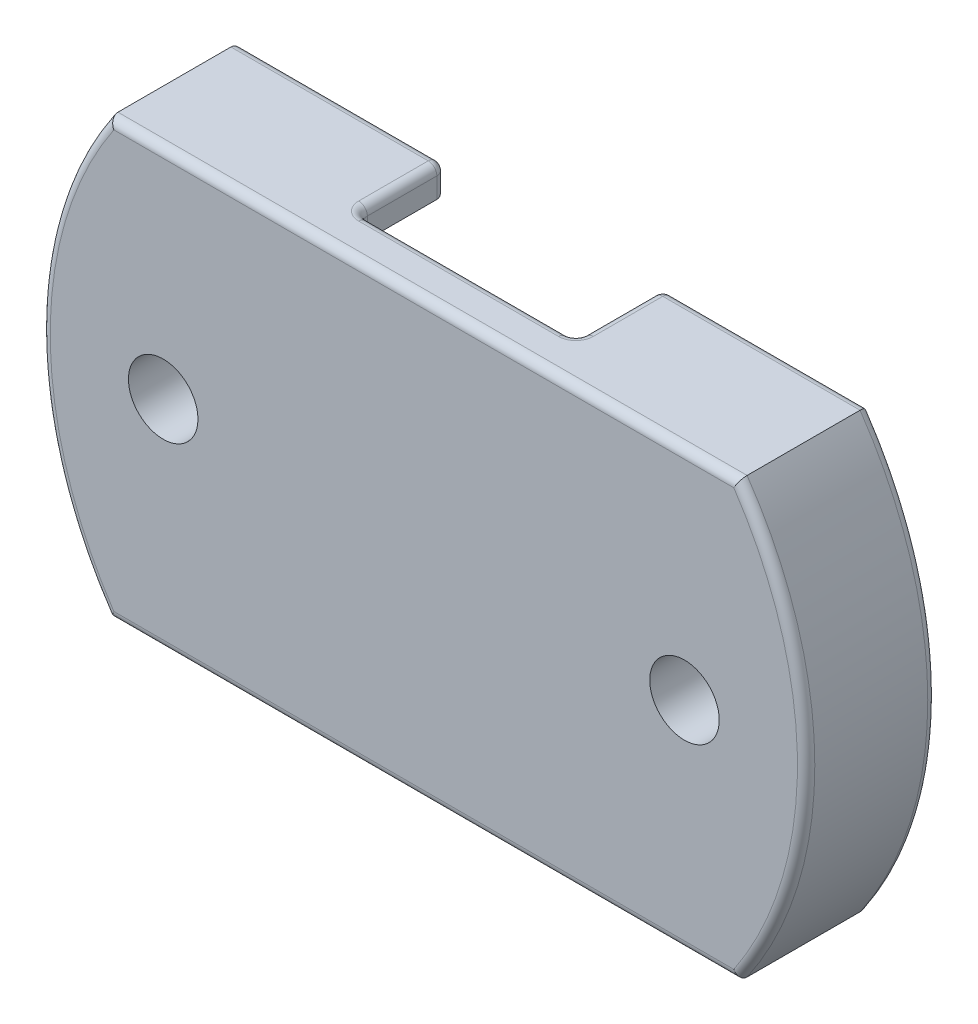
SolidWorks part; units mm, degrees
ref_plane "Front Plane" through (0, 0, 0) normal (0, 0, 1) x (1, 0, 0)
ref_plane "Top Plane" through (0, 0, 0) normal (0, 1, 0) x (1, 0, 0)
ref_plane "Right Plane" through (0, 0, 0) normal (1, 0, 0) x (0, 0, -1)
sketch "Sketch1" plane through (0, 0, 0) normal (0, 0, 1) x (1, 0, 0)
  line L0 (-73.039, 0) -> (73.039, 0) construction
  line L1 (-73.039, -25) -> (73.039, -25)
  line L2 (-73.039, 25) -> (73.039, 25)
  circle A0 centre (0, 0) radius 30
  circle A1 centre (-30, 0) radius 4
  circle A2 centre (30, 0) radius 4
  circle A3 centre (0, 0) radius 44
  circle A4 centre (0, 0) radius 17.5
  dimension "D1" = 60
  dimension "D2" = 8
  dimension "D3" = 88
  dimension "D6" = 35
  dimension "D4" = 25
  dimension "D5" = 25
sketch "Sketch2" plane through (0, 0, 0) normal (0, 0, 1) x (1, 0, 0)
  line L0 (-73.039, 25) -> (73.039, 25) construction
  line L1 (-73.039, -25) -> (73.039, -25) construction
  line L2 (-36.2077, 25) -> (36.2077, 25)
  line L3 (-36.2077, -25) -> (36.2077, -25)
  arc A0 (36.2077, -25) -> (36.2077, 25) centre (0, 0) ccw
  circle A1 centre (0, 0) radius 44
  arc A2 (-36.2077, 25) -> (-36.2077, -25) centre (0, 0) ccw
  dimension "D1" = 0
extrude "Boss-Extrude1" add sketch "Sketch2" along normal blind 15
sketch "Sketch3" plane through (0, 0, 0) normal (0, 0, 1) x (1, 0, 0)
  line L0 (12.5, 21.6506) -> (12.5, 42.5593)
  line L5 (12.5, -42.5593) -> (-12.5, -42.5593)
  line L6 (12.5, -42.5593) -> (12.5, -21.6506)
  line L7 (12.5, 42.5593) -> (-12.5, 42.5593)
  line L8 (-12.5, -42.5593) -> (-12.5, -21.6506)
  line L9 (12.5, -42.5593) -> (-12.5, 42.5593) construction
  line L10 (12.5, 42.5593) -> (-12.5, -42.5593) construction
  line L11 (-12.5, 21.6506) -> (-12.5, 42.5593)
  arc A0 (-12.5, 21.6506) -> (-12.5, -21.6506) centre (0, 0) ccw
  arc A3 (12.5, -21.6506) -> (12.5, 21.6506) centre (0, 0) ccw
  dimension "D1" = 50
  dimension "D2" = 25
extrude "Cut-Extrude1" cut sketch "Sketch3" along normal blind 10
fillet "Fillet1" radius 1 24 edges at (0, -25, 10) (0, 25, 10) (-24.3539, 25, 0) (-44, 0, 0) (-24.3539, -25, 0) (24.3539, -25, 0) (44, 0, 0) (24.3539, 25, 0) (12.5, 25, 5) (-12.5, 25, 5) (-12.5, -25, 5) (12.5, -25, 5) (-12.5, 23.3253, 10) (-25, 0, 10) (-12.5, -23.3253, 10) (12.5, -23.3253, 10) (25, 0, 10) (12.5, 23.3253, 10) (-25, 0, 0) (-12.5, 23.3253, 0) (-12.5, -23.3253, 0) (12.5, 23.3253, 0) (25, 0, 0) (12.5, -23.3253, 0)
fillet "Fillet2" radius 1 4 edges at (0, -25, 15) (-44, 0, 15) (0, 25, 15) (44, 0, 15)
sketch "Sketch4" plane through (0, 0, 15) normal (0, 0, 1) x (1, 0, 0)
  circle A0 centre (-30, 0) radius 4 construction
  circle A1 centre (30, 0) radius 4 construction
  circle A2 centre (-30, 0) radius 4
  circle A3 centre (30, 0) radius 4
extrude "Cut-Extrude2" cut sketch "Sketch4" against normal through all
